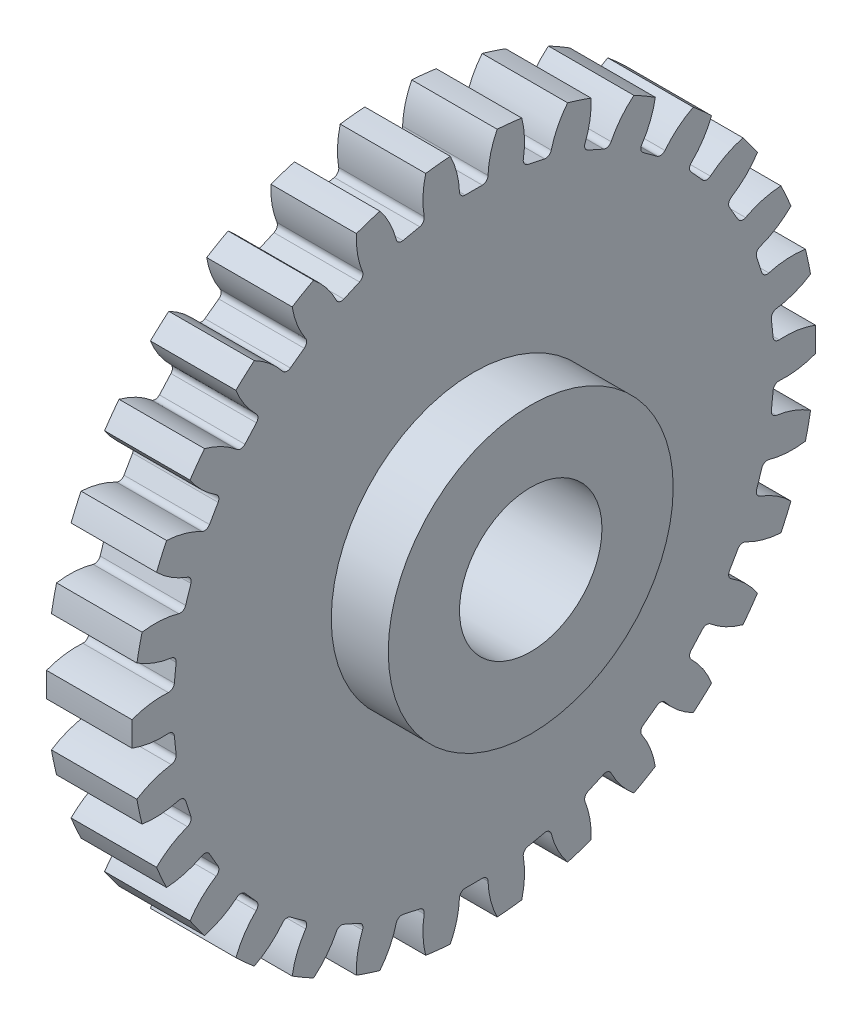
SolidWorks part; units mm, degrees
ref_plane "Front Plane" through (0, 0, 0) normal (0, 0, 1) x (1, 0, 0)
ref_plane "Top Plane" through (0, 0, 0) normal (0, 1, 0) x (1, 0, 0)
ref_plane "Right Plane" through (0, 0, 0) normal (1, 0, 0) x (0, 0, -1)
sketch "Sketch1" plane through (0, 0, 0) normal (1, 0, 0) x (0, 0, -1)
  circle A0 centre (0, 0) radius 18
  dimension "D1" = 36
extrude "Boss-Extrude1" add sketch "Sketch1" along normal mid plane 4.5
sketch "Sketch2" plane through (2.25, 0, 0) normal (1, 0, 0) x (0, 0, -1)
  circle A0 centre (0, 0) radius 3.75
  circle A1 centre (0, 0) radius 7.5
  circle A2 centre (0, 0) radius 2.25
  dimension "D1" = 7.5
  dimension "D2" = 15
  dimension "D3" = 4.5
extrude "Boss-Extrude2" add sketch "Sketch2" along normal blind 3 contours A1 A0 region at (2.25, 0, 7.2879)
extrude "Cut-Extrude1" cut sketch "Sketch2<2>" against normal blind 2.5 contours A0 region at (2.25, 0, 3.6439)
sketch "Sketch2<2>" plane through (2.25, 0, 0) normal (1, 0, 0) x (0, 0, -1) same geometry as "Sketch2"
extrude "Cut-Extrude2" cut sketch "Sketch2<4>" against normal through all contours A2 region at (2.25, 0, 0)
sketch "Sketch2<4>" plane through (2.25, 0, 0) normal (1, 0, 0) x (0, 0, -1) same geometry as "Sketch2"
sketch "Sketch3" plane through (2.25, 0, 0) normal (1, 0, 0) x (0, 0, -1)
  line L0 (0, 0) -> (0, 20.0785) construction
  line L1 (-0.4523, 15.8) -> (0.4523, 15.8)
  line L2 (-2.03, 19.08) -> (2.03, 19.08)
  arc A0 (0.7521, 16.0883) -> (2.03, 19.08) centre (5.3087, 15.9108) cw
  arc A1 (-0.7521, 16.0883) -> (-2.03, 19.08) centre (-5.3087, 15.9108) ccw
  arc A2 (0.4523, 15.8) -> (0.7521, 16.0883) centre (0.4523, 16.1) ccw
  arc A3 (-0.7521, 16.0883) -> (-0.4523, 15.8) centre (-0.4523, 16.1) ccw
  circle A4 centre (0, 0) radius 18 construction
  point P6 (0, 0)
  point P15 (0, 15.8)
  point P17 (0.75, 15.8)
  point P20 (-0.75, 15.8)
  dimension "D4" = 4.56
  dimension "D5" = 0.3
  dimension "D1" = 0.75
  dimension "D2" = 3.28
  dimension "D3" = 1.28
  dimension "D6" = 15.8
extrude "Cut-Extrude3" cut sketch "Sketch3" against normal through all
pattern_circular "CirPattern1" count 30 over 360 about axis through (2.25, 0, 0) along (-1, 0, 0) of "Cut-Extrude3"
